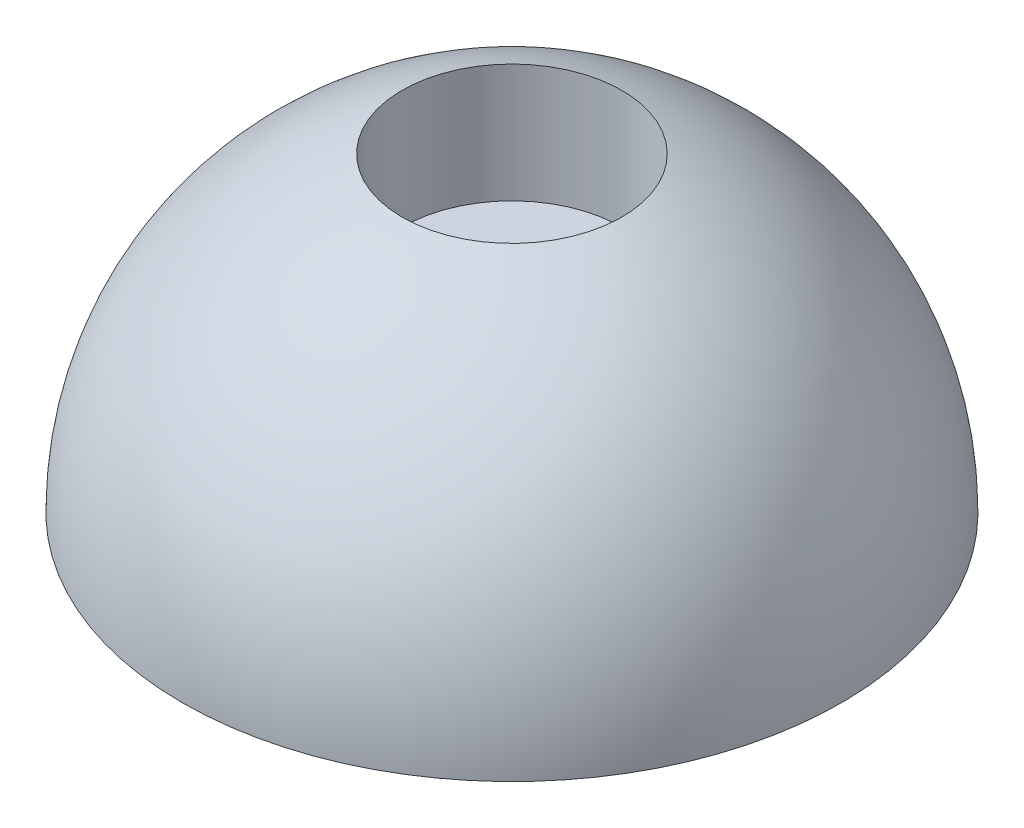
SolidWorks part; units mm, degrees
ref_plane "Front Plane" through (0, 0, 0) normal (0, 0, 1) x (1, 0, 0)
ref_plane "Top Plane" through (0, 0, 0) normal (0, 1, 0) x (1, 0, 0)
ref_plane "Right Plane" through (0, 0, 0) normal (1, 0, 0) x (0, 0, -1)
sketch "Sketch1" plane through (0, 0, 0) normal (0, 0, 1) x (1, 0, 0)
  line L0 (0, 0) -> (3.302, 0) construction
  line L1 (0, -2.7781) -> (0, 2.7781) construction
  line L2 (0, 2.7781) -> (6.35, 2.7781) construction
  line L3 (0, -2.7781) -> (6.35, -2.7781) construction
  line L4 (0, 8.3344) -> (0, 2.7781) construction
  line L5 (0, -2.7781) -> (0, -8.3344) construction
  line L6 (0, -8.3344) -> (6.35, -8.3344)
  line L7 (6.35, -8.3344) -> (6.35, -2.7781)
  line L8 (3.302, 0) -> (3.302, -2.7781)
  line L9 (3.302, -2.7781) -> (6.35, -2.7781)
  line L10 (3.302, 0) -> (3.302, 2.7781)
  line L11 (3.302, 2.7781) -> (6.35, 2.7781)
  line L12 (6.35, 2.7781) -> (6.35, 8.3344)
  line L13 (6.35, -8.3344) -> (19.05, -8.3344)
  line L14 (6.35, 8.3344) -> (6.35, 9.6261)
  circle A0 centre (0, -8.3344) radius 19.05
  point P22 (19.05, -8.3344)
revolve "Revolve1" add sketch "Sketch1" angle 360 about L5 region at (10.9836, -1.0444, 0)
ref_axis "Axis1" through (0, -2.7781, 0) along (0, 1, 0)
